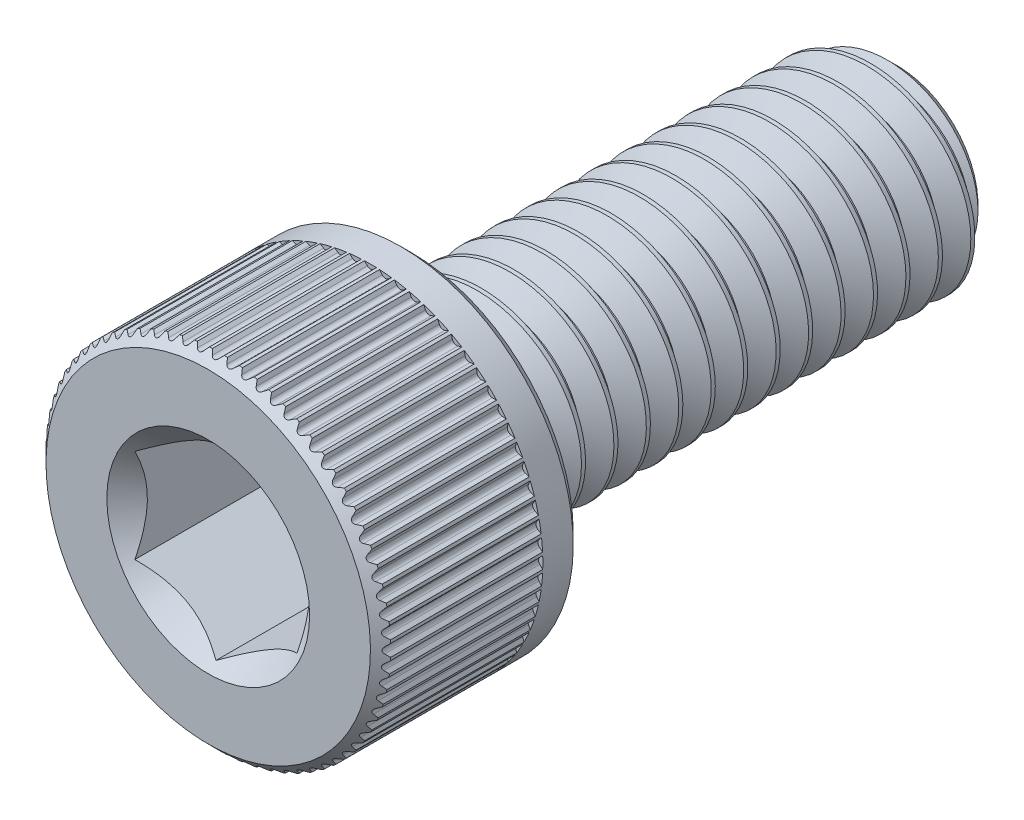
SolidWorks part; units mm, degrees
ref_plane "Front Plane" through (0, 0, 0) normal (0, 0, 1) x (1, 0, 0)
ref_plane "Top Plane" through (0, 0, 0) normal (0, 1, 0) x (1, 0, 0)
ref_plane "Right Plane" through (0, 0, 0) normal (1, 0, 0) x (0, 0, -1)
sketch "Sketch1" plane through (0, 0, 0) normal (1, 0, 0) x (0, 0, -1)
  line L0 (-8.5, 0) -> (8.5, 0) construction
  line L1 (8.5, 0) -> (8.5, 1.9804) construction
  line L2 (8.5, 1.9804) -> (7.9804, 2.5) construction
  line L3 (7.9804, 2.5) -> (7.9, 2.5) construction
  line L4 (7.9, 2.5) -> (-3.5, 2.5) construction
  line L5 (-3.5, 2.5) -> (-3.5, 4.25) construction
  line L6 (-3.5, 4.25) -> (-8.5, 4.25) construction
  line L7 (-8.5, 4.25) -> (-8.5, 0) construction
  line L8 (8.5, 1.9804) -> (8.5, 2.5) construction
  line L9 (8.45, 2.5866) -> (8.85, 1.8938) construction
  line L10 (8.85, 1.8938) -> (9.25, 2.5866) construction
  line L11 (9.25, 2.5866) -> (8.45, 2.5866) construction
  line L12 (8.85, 2.5866) -> (8.85, 2.5) construction
  line L13 (8.85, 1.8938) -> (8.85, 1.9804) construction
  line L14 (8.8, 1.9804) -> (8.9, 1.9804) construction
  line L15 (8.5, 2.5) -> (9.2, 2.5) construction
  line L16 (8.475, 2.5433) -> (9.225, 2.5433) construction
  line L17 (8.5, 0) -> (8.5, -2.5) construction
  line L18 (-3.75, 4.25) -> (-3.5, 4) construction
  line L19 (-8.25, 4.25) -> (-8.5, 4) construction
  line L20 (-3.5, 2.5) -> (-3.5, 0) construction
  line L21 (-3.5, 1.25) -> (0.5, 1.25) construction
  line L22 (0.5, 1.25) -> (4.5, 1.25) construction
  line L23 (4.5, 1.25) -> (8.5, 1.25) construction
  line L24 (0.5, 1.25) -> (0.5, 2.5) construction
  line L25 (0.5, 2.5) -> (0.5, 4.25) construction
  line L26 (4.5, 1.25) -> (4.5, 4.25) construction
  point P0 (-8.5, 2)
  point P3 (6.5, 2.5)
  point P4 (0, 0)
  point P18 (4.5, 2.5)
  point P22 (8.85, 1.9804)
  point P24 (7.9, 2.5)
  point P25 (8.85, 2.5)
  point P28 (8.85, 2.5433)
  point P29 (6.5, -2.5)
  point P30 (0.5, 2.5)
  point P31 (-6, 4.25)
  point P37 (-4.375, 4.25)
  point P38 (-8.125, 4.25)
  point P45 (0.5, 1.25)
  point P46 (4.5, 1.25)
  dimension "D7" = 0.25
  dimension "D8" = 0.25
  dimension "D9" = 0.25
  dimension "D10" = 0.125
  dimension "D11" = 0.625
  dimension "Drive Size" = 4
  dimension "Head Diameter" = 8.5
  dimension "Head Height" = 5
  dimension "Thread Pitch" = 0.8
  dimension "Thread Size" = 5
  dimension "Length" = 12
  dimension "D12" = 0.6
  dimension "D4" = 2
  dimension "D3" = 45
sketch "Sketch2" plane through (0, 0, 0) normal (1, 0, 0) x (0, 0, -1)
  line L0 (-8.5, 0) -> (-8.5, 4)
  line L1 (-8.25, 4.25) -> (-3.75, 4.25)
  line L2 (-3.5, 4) -> (-3.5, 2.75)
  line L4 (7.9804, 2.5) -> (8.5, 1.9804)
  line L5 (8.5, 1.9804) -> (8.5, 0)
  line L6 (-3.5, 4.25) -> (-8.5, 4.25) construction
  line L7 (8.5, 0) -> (-8.5, 0)
  line L8 (-8.25, 4.25) -> (-8.5, 4) construction
  line L10 (-8.25, 4.25) -> (-8.5, 4)
  line L14 (-3.75, 4.25) -> (-3.5, 4) construction
  line L16 (-3.75, 4.25) -> (-3.5, 4)
  line L17 (-3.5, 2.5) -> (-3.5, 4.25) construction
  line L19 (-3.25, 2.5) -> (7.9804, 2.5)
  line L20 (7.9, 2.5) -> (-3.5, 2.5) construction
  arc A1 (-3.5, 2.75) -> (-3.25, 2.5) centre (-3.25, 2.75) ccw
  dimension "D3" = 0.25
revolve "Revolve1" add sketch "Sketch2" angle 360 about L7
sketch "Sketch3" plane through (0, 0, 8.5) normal (0, 0, 1) x (1, 0, 0)
  line L1 (2, -1.1547) -> (2, 1.1547)
  line L2 (2, 1.1547) -> (0, 2.3094)
  line L3 (0, 2.3094) -> (-2, 1.1547)
  line L4 (-2, 1.1547) -> (-2, -1.1547)
  line L5 (-2, -1.1547) -> (0, -2.3094)
  line L6 (0, -2.3094) -> (2, -1.1547)
  circle A0 centre (0, 0) radius 2 construction
  circle A1 centre (0, 0) radius 4.25 construction
  circle A2 centre (0, 0) radius 4.25 construction
  circle A3 centre (0, 0) radius 2.3094 construction
  point P13 (0, 0)
extrude "Cut-Extrude1" cut sketch "Sketch3" against normal offset from surface (4 mm away) 1 up to face at (0, 4, 3.5)
sketch "Sketch4" plane through (0, 0, 8.5) normal (0, 0, 1) x (1, 0, 0)
  circle A0 centre (0, 0) radius 2.5
  dimension "D1" = 5
extrude "Cut-Extrude2" cut sketch "Sketch4" against normal up to vertex (2.5 mm away) draft 45 up to point (0, 4.25, 6)
sketch "Sketch11" plane through (0, 0, 0) normal (1, 0, 0) x (0, 0, -1)
  line L0 (-8.5, 0) -> (8.5, 0) construction
  line L1 (-8.5, 0) -> (8.5, 0) construction
  line L2 (-1.25, 0) -> (-1.25, 2.5) construction
  line L3 (7.9, 2.5) -> (-3.5, 2.5) construction
  line L4 (6.25, 0) -> (6.25, 2.5) construction
  line L6 (8.5, 1.9804) -> (8.5, 2.5) construction
  point P2 (-1.25, 0)
  point P3 (6.25, 0)
  dimension "D1" = 2.25
  dimension "D2" = 2.25
sketch "Sketch6" plane through (0, 0, -8.5) normal (0, 0, -1) x (-1, 0, 0)
  circle A0 centre (0, 0) radius 2.5
curve "Helix/Spiral1" pitch 0.8 height 12.8 radius 2.5 centre (0, 0, -8.5) axis (0, 0, 1) start towards (0, 1, 0)
sketch "Sketch10" plane through (0, 0, 0) normal (1, 0, 0) x (0, 0, -1)
  line L0 (-3.25, -4.25) -> (-3.25, 4.25)
  line L5 (-8.5, 0) -> (8.5, 0) construction
  line L6 (-3.25, 2.5) -> (-3.25, -2.5) construction
  point P3 (-3.25, 0)
split "Split1" trim tools "Sketch10" bodies to split 106 resulting bodies 114 115
sketch "Sketch7" plane through (0, 0, 0) normal (1, 0, 0) x (0, 0, -1)
  line L0 (8.475, 2.5433) -> (9.225, 2.5433)
  line L1 (9.225, 2.5433) -> (8.9, 1.9804)
  line L2 (8.9, 1.9804) -> (8.8, 1.9804)
  line L3 (8.8, 1.9804) -> (8.475, 2.5433)
sweep "Cut-Sweep1" cut profiles "Sketch7" path "Helix/Spiral1" align with end faces yes
sketch "Sketch8" plane through (0, 0, 0) normal (1, 0, 0) x (0, 0, -1)
  line L0 (-3.5, 0) -> (-3.5, 2.5)
  line L1 (-3.25, -2.5) -> (-3.25, 2.5) construction
  line L2 (-3.5, 2.5) -> (-3.25, 2.5)
  line L4 (-3.25, 2.5) -> (-1.8066, 0)
  line L5 (-1.8066, 0) -> (-3.5, 0)
  line L6 (7.9, 2.5) -> (-3.5, 2.5) construction
  line L7 (-8.5, 0) -> (8.5, 0) construction
  dimension "D1" = 60
revolve "Revolve2" add sketch "Sketch8" angle 360 about L5
ref_plane "Plane1" through (0, 0, 8.5) normal (0, 0, 1) x (1, 0, 0)
sketch "Sketch12" plane through (0, 0, 8.5) normal (0, 0, 1) x (1, 0, 0)
  line L0 (0, 0) -> (0.1483, 4.2474) construction
  line L1 (0, 0) -> (-0.1483, 4.2474) construction
  line L2 (0, 4.1437) -> (0, 4.3563) construction
  line L3 (-0.2572, 4.3563) -> (0.2572, 4.3563)
  line L4 (-0.2572, 4.3563) -> (-0.0762, 4.1753)
  line L5 (0.0762, 4.1753) -> (0.2572, 4.3563)
  circle A0 centre (0, 0) radius 4.25 construction
  arc A1 (-0.0762, 4.1753) -> (0.0762, 4.1753) centre (0, 4.2516) ccw
  point P9 (0, 4.3563)
  point P13 (0, 4.25)
  dimension "D1" = 4
  dimension "D2" = 0.1063
extrude "Cut-Extrude3" cut sketch "Sketch12" against normal blind 4
pattern_circular "CirPattern1" count 72 over 360 about axis through (0, 0, 8.5) along (0, 0, -1) of "Cut-Extrude3"
equation "\"D2@Sketch1\" = \"Thread Pitch@Sketch1\" / 8"
equation "\"D4@Helix/Spiral1\" = \"Thread Pitch@Sketch1\""
equation "\"D7@Sketch1\" = \"Head Height@Sketch1\" * .05"
equation "\"D8@Sketch1\"=\"D7@Sketch1\""
equation "\"D9@Sketch1\"=\"D7@Sketch1\""
equation "\"D10@Sketch1\"=\"D7@Sketch1\"/2"
equation "\"D11@Sketch1\"=\"D10@Sketch1\"*5"
equation "\"D4@Sketch1\"=\"Thread Pitch@Sketch1\"*2.5"
equation "\"D12@Sketch1\"=\"Thread Pitch@Sketch1\"*.75"
equation "\"D3@Helix/Spiral1\"=\"Length@Sketch1\"+\"Thread Pitch@Sketch1\""
equation "\"D3@Sketch2\" = \"Thread Size@Sketch1\" * 0.05"
equation "\"D1@Sketch11\"=\"Length@Sketch1\"*0.1875"
equation "\"D2@Sketch11\"=\"D1@Sketch11\""
equation "\"D2@Sketch12\"=\"Head Diameter@Sketch1\"*.0125"
equation "\"D1@Cut-Extrude3\"=\"Head Height@Sketch1\"*.8"
equation "\"D1@CirPattern1\"=\"D3@CirPattern1\"/(1.25*\"D1@Sketch12\")"
equation "\"D1@Sketch4\"=\"Drive Size@Sketch1\"*1.25"
